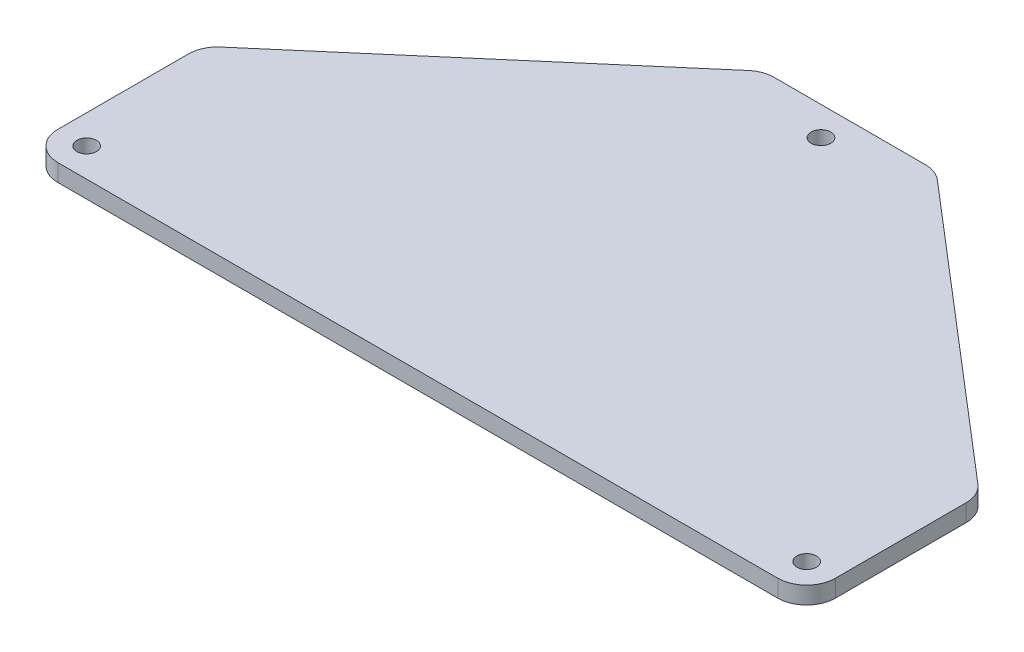
SolidWorks part; units mm, degrees
ref_plane "Front" through (0, 0, 0) normal (0, 0, 1) x (1, 0, 0)
ref_plane "Top" through (0, 0, 0) normal (0, 1, 0) x (1, 0, 0)
ref_plane "Right" through (0, 0, 0) normal (1, 0, 0) x (0, 0, -1)
sketch "Esquisse1" plane through (0, 0, 0) normal (0, 1, 0) x (1, 0, 0)
  line L0 (-67.5, 0) -> (67.5, 0)
  line L1 (0, 0) -> (67.5, 0) construction
  line L2 (0, 0) -> (0, 75) construction
  line L3 (0, 75) -> (67.5, 75) construction
  line L4 (67.5, 0) -> (67.5, 75) construction
  line L5 (67.5, 0) -> (67.5, 30)
  line L6 (67.5, 30) -> (15, 75)
  line L7 (15, 75) -> (-15, 75)
  line L8 (-67.5, 30) -> (-15, 75)
  line L9 (-67.5, 0) -> (-67.5, 30)
  dimension "D1" = 67.5
  dimension "D2" = 30
  dimension "D3" = 15
  dimension "D4" = 75
extrude "Boss.-Extru.1" add sketch "Esquisse1" along normal blind 3
fillet "Congé1" radius 5 6 edges at (-67.5, 1.5, 0) (-67.5, 1.5, -30) (-15, 1.5, -75) (15, 1.5, -75) (67.5, 1.5, -30) (67.5, 1.5, 0)
sketch "Esquisse2" plane through (0, 3, 0) normal (0, 1, 0) x (1, 0, 0)
  line L0 (-62.5, 0) -> (62.5, 0) construction
  line L1 (67.5, 5) -> (67.5, 27.7003) construction
  circle A0 centre (-62.5, 5) radius 1
  circle A1 centre (62.5, 5) radius 1
  circle A2 centre (0, 70) radius 1
  dimension "D4" = 2
  dimension "D5" = 2
  dimension "D6" = 2
  dimension "D1" = 62.5
  dimension "D2" = 62.5
  dimension "D3" = 65
  dimension "D7" = 5
  dimension "D8" = 5
  dimension "D9" = 67.5
hole_wizard "Dégagement M31" positions "Esquisse3" profile "Esquisse4" hole size "M3" standard "ISO"
sketch "Esquisse3" plane through (0, 3, 0) normal (0, 1, 0) x (1, 0, 0)
  point P0 (-62.5, 5)
  point P3 (62.5, 5)
  point P6 (0, 70)
sketch "Esquisse4" plane through (-62.5, 3, -5) normal (1, 0, 0) x (0, 0, 1)
  line L0 (0, 0) -> (0, 11.0215)
  line L1 (0, 11.0215) -> (1.7, 10)
  line L2 (1.7, 10) -> (1.7, 0)
  line L5 (1.7, 0) -> (0, 0)
  line L10 (0, 11.0215) -> (-1.7, 10) construction
  line L11 (0, -6.35) -> (0, 107.95) construction
  dimension "Diamètre du perçage" = 3.4
  dimension "Profondeur du perçage" = 10
  dimension "Angle de pointe" = 118
equation "\"D1@Esquisse1\"=135/2"
equation "\"D1@Esquisse2\"=125/2"
